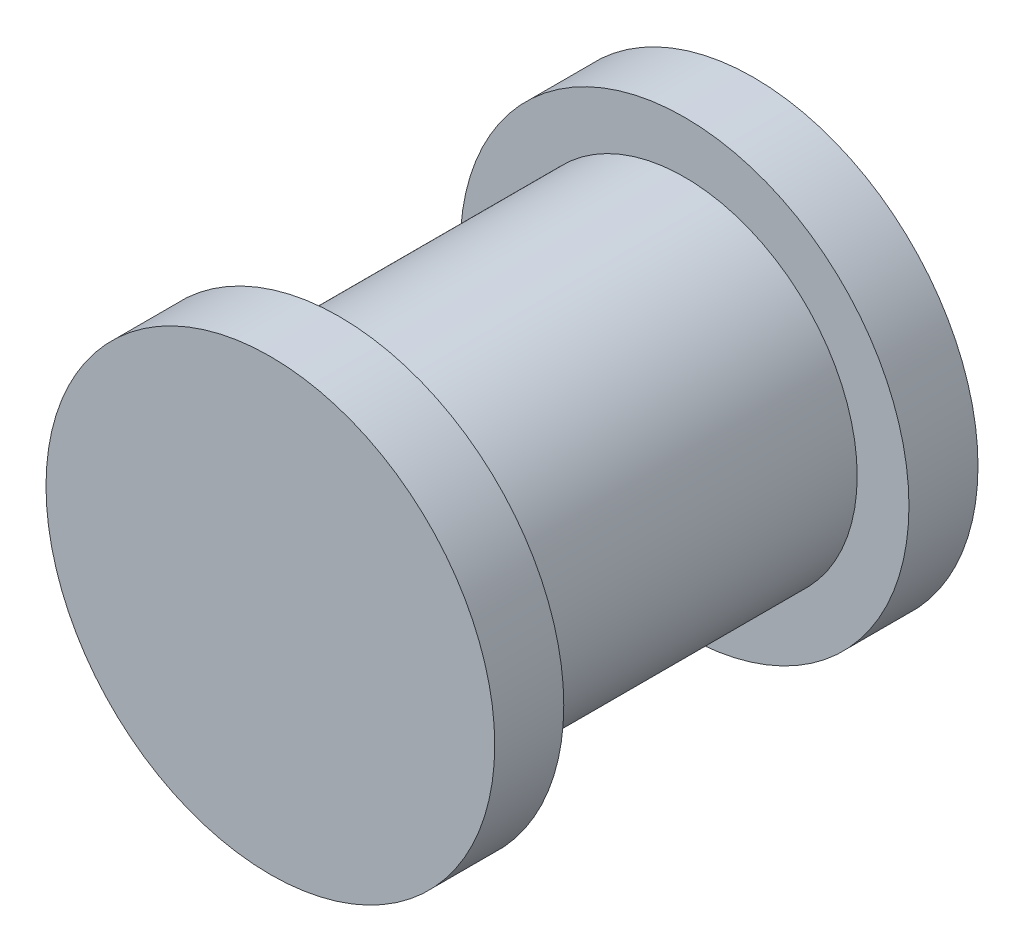
SolidWorks part; units mm, degrees
ref_plane "Front Plane" through (0, 0, 0) normal (0, 0, 1) x (1, 0, 0)
ref_plane "Top Plane" through (0, 0, 0) normal (0, 1, 0) x (1, 0, 0)
ref_plane "Right Plane" through (0, 0, 0) normal (1, 0, 0) x (0, 0, -1)
sketch "Sketch1" plane through (0, 0, 0) normal (0, 0, 1) x (1, 0, 0)
  circle A0 centre (0, 0) radius 250
  dimension "D1" = 500
extrude "Boss-Extrude1" add sketch "Sketch1" along normal blind 500 contours A0
sketch "Sketch2" plane through (0, 0, 500) normal (0, 0, 1) x (1, 0, 0)
  circle A0 centre (0, 0) radius 325
  dimension "D1" = 650
extrude "Boss-Extrude2" add sketch "Sketch2" along normal blind 100
sketch "Sketch3" plane through (0, 0, 0) normal (0, 0, -1) x (-1, 0, 0)
  circle A0 centre (0, 0) radius 325
  dimension "D1" = 650
extrude "Boss-Extrude3" add sketch "Sketch3" along normal blind 100
